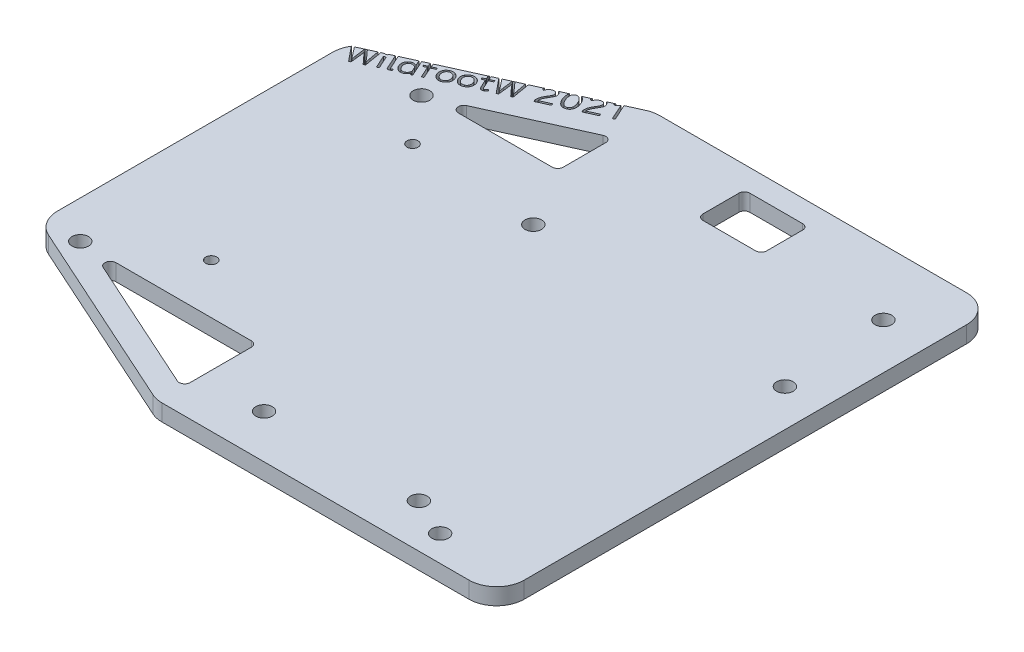
SolidWorks part; units mm, degrees
ref_plane "Front Plane" through (0, 0, 0) normal (0, 0, 1) x (1, 0, 0)
ref_plane "Top Plane" through (0, 0, 0) normal (0, 1, 0) x (1, 0, 0)
ref_plane "Right Plane" through (0, 0, 0) normal (1, 0, 0) x (0, 0, -1)
ref_plane "Plane1" through (0, 33, 0) normal (0, 1, 0) x (1, 0, 0)
sketch "Sketch1" plane through (0, 33, 0) normal (0, 1, 0) x (1, 0, 0)
  line L1 (1.5705, -45) -> (101.5705, -45)
  line L2 (1.5705, -45) -> (1.5705, 45)
  line L3 (1.5705, 45) -> (101.5705, 45)
  line L4 (101.5705, -45) -> (101.5705, 45)
  line L6 (1.5705, 27.6462) -> (39.9782, 45)
  line L8 (1.5705, 27.6462) -> (39.9782, 27.6462) construction
  line L9 (39.9782, 27.6462) -> (39.9782, 45) construction
  line L10 (6.0167, 0) -> (1.5705, 0) construction
  line L11 (6.0167, 23.2) -> (6.0167, -23.2) construction
  line L12 (39.9782, 27.6462) -> (39.9782, 23.2) construction
  line L13 (40.3167, 23.2) -> (6.0167, 23.2) construction
  line L14 (39.9782, 27.6462) -> (44.4243, 27.6462) construction
  line L15 (44.4243, 28.4878) -> (44.4243, -37.1122) construction
  line L16 (1.5705, -27.6462) -> (39.9782, -45)
  line L17 (101.5705, 0) -> (97.1243, 0) construction
  line L19 (97.1243, -37.1122) -> (97.1243, 28.4878) construction
  point P4 (101.5705, 0)
  point P6 (1.5705, 0)
  dimension "D1" = 100
  dimension "D2" = 90
extrude "Boss-Extrude1" add sketch "Sketch1" along normal blind 3 contours L2 L1 L4 L3 region at (54.5456, 33, 0)
sketch "Sketch2" plane through (0, 33, 0) normal (0, -1, 0) x (1, 0, 0)
  line L1 (3.515, -25.123) -> (36.4444, -40.0016) construction
  line L2 (1.5705, -27.6462) -> (39.9782, -45) construction
  text T0 "WildfootW 2021" font "@BIZ UDPGothic" height 3.5
  dimension "D1" = 3.1
extrude "Cut-Extrude1" cut sketch "Sketch2" against normal up to surface (3 mm away) up to face at (47.7064, 36, 0)
sketch "Sketch3" plane through (0, 33, 0) normal (0, 1, 0) x (1, 0, 0)
  line L0 (17.8264, 27.2) -> (40.4243, 37.4105)
  line L1 (40.4243, 37.4105) -> (40.4243, 27.2)
  line L2 (40.4243, 27.2) -> (17.8264, 27.2)
  line L3 (3.515, 25.123) -> (36.4444, 40.0016) construction
  line L4 (10.2976, -27.2) -> (40.4243, -27.2)
  line L5 (40.4243, -27.2) -> (40.4243, -40.8122)
  line L6 (40.4243, -40.8122) -> (10.2976, -27.2)
  line L7 (1.5705, -27.6462) -> (39.9782, -45) construction
  line L8 (40.4243, -27.2) -> (40.4243, -23.2) construction
  line L9 (44.4243, 28.4878) -> (44.4243, -37.1122) construction
  line L10 (44.4243, -27.2) -> (40.4243, -27.2) construction
  line L11 (6.0167, -23.2) -> (40.3167, -23.2) construction
  line L12 (25.361, -34.0061) -> (23.714, -37.6513) construction
  line L13 (40.4243, 27.2) -> (40.4243, 23.2) construction
  line L14 (40.3167, 23.2) -> (6.0167, 23.2) construction
  line L15 (40.4243, 27.2) -> (44.4243, 27.2) construction
  line L16 (29.1254, 32.3052) -> (27.4783, 35.9504) construction
  line L17 (56.4243, 31.8878) -> (60.3791, 32.4878) construction
  line L18 (60.3791, 32.4878) -> (71.9243, 32.4878)
  line L19 (60.3791, 32.4878) -> (60.3791, 41)
  line L20 (60.3791, 41) -> (71.9243, 41)
  line L21 (71.9243, 32.4878) -> (71.9243, 41)
  line L22 (60.3791, 32.4878) -> (60.3791, 28.4878) construction
  line L23 (75.9243, 28.4878) -> (56.4243, 28.4878) construction
  line L24 (71.9243, 32.4878) -> (75.9243, 32.4878) construction
  line L25 (75.9243, 35.7878) -> (75.9243, 19.1878) construction
  line L26 (71.9243, 41) -> (71.9243, 45) construction
  line L27 (39.9782, 45) -> (101.5705, 45) construction
  dimension "D1" = 4
extrude "Cut-Extrude2" cut sketch "Sketch3" along normal up to surface (3 mm away) up to face at (18.3525, 36, -33.0193)
fillet "Fillet1" radius 5 6 edges at (101.5705, 34.5, 45) (39.9782, 34.5, 45) (1.5705, 34.5, 27.6462) (1.5705, 34.5, -27.6462) (39.9782, 34.5, -45) (101.5705, 34.5, -45)
fillet "Fillet2" radius 1 10 edges at (60.3791, 34.5, -41) (71.9243, 34.5, -41) (40.4243, 34.5, -37.4105) (17.8264, 34.5, -27.2) (60.3791, 34.5, -32.4878) (71.9243, 34.5, -32.4878) (40.4243, 34.5, -27.2) (40.4243, 34.5, 40.8122) (40.4243, 34.5, 27.2) (10.2976, 34.5, 27.2)
sketch "Sketch4" plane through (0, 33, 0) normal (0, 1, 0) x (1, 0, 0)
  circle A0 centre (8.3674, -27.0854) radius 1.5
  circle A1 centre (86.6598, -40.308) radius 1.5
  circle A2 centre (93.3054, 33.2195) radius 1.5
  circle A3 centre (16.3794, 26.6064) radius 1.5
  circle A4 centre (16.3794, 26.6064) radius 1.5 construction
  circle A5 centre (93.3054, 33.2195) radius 1.5 construction
  circle A6 centre (86.6598, -40.308) radius 1.5 construction
  circle A7 centre (8.3674, -27.0854) radius 1.5 construction
  circle A8 centre (23.1667, -18.2) radius 1
  circle A9 centre (23.1667, 18.2) radius 1
  circle A10 centre (94.8243, 13.8878) radius 1.5
  circle A11 centre (46.7243, 16.4878) radius 1.5
  circle A12 centre (51.6243, -37.1122) radius 1.5
  circle A13 centre (79.6243, -37.1122) radius 1.5
  circle A14 centre (79.6243, -37.1122) radius 1.5 construction
  circle A15 centre (51.6243, -37.1122) radius 1.5 construction
  circle A16 centre (23.1667, -18.2) radius 1 construction
  circle A17 centre (23.1667, 18.2) radius 1 construction
  arc A18 (47.4243, 17.8144) -> (47.6243, 17.6878) centre (46.7243, 16.4878) ccw construction
  circle A19 centre (94.8243, 13.8878) radius 1.5 construction
extrude "Cut-Extrude3" cut sketch "Sketch4" along normal up to surface (3 mm away) up to face at (18.3525, 36, -33.0193)
